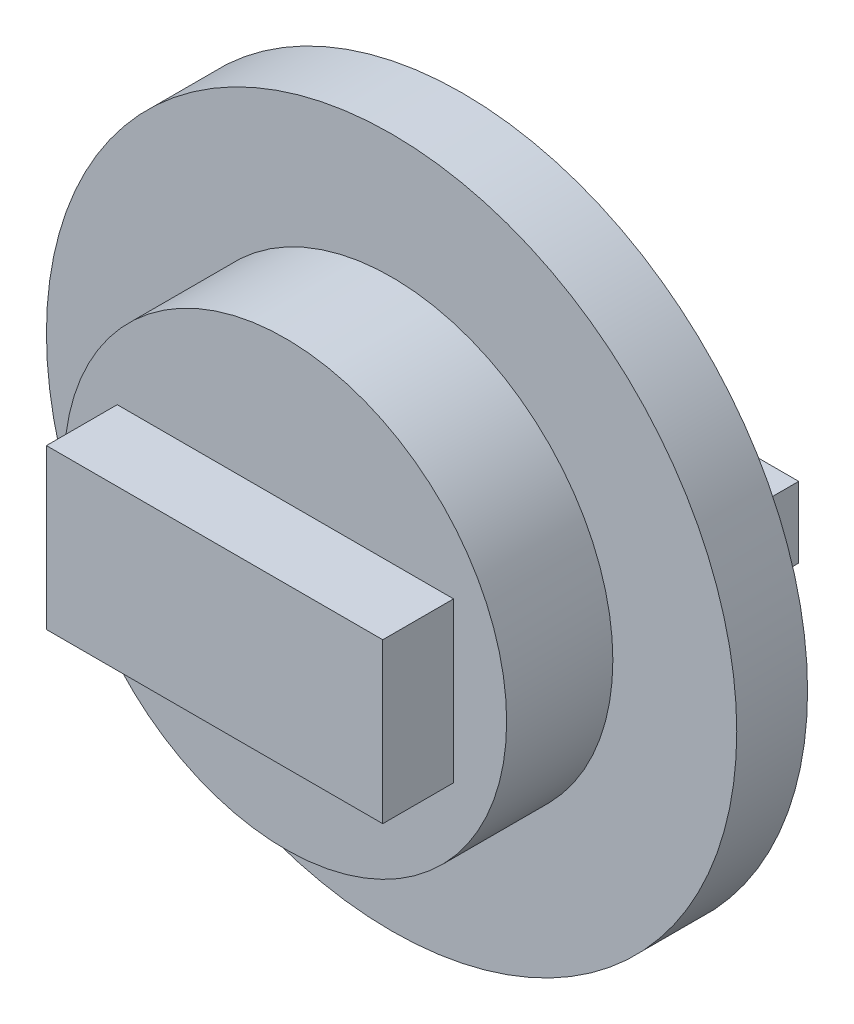
SolidWorks part; units mm, degrees
ref_plane "Спереди" through (0, 0, 0) normal (0, 0, 1) x (1, 0, 0)
ref_plane "Сверху" through (0, 0, 0) normal (0, 1, 0) x (1, 0, 0)
ref_plane "Справа" through (0, 0, 0) normal (1, 0, 0) x (0, 0, -1)
sketch "Эскиз1" plane through (0, 0, 0) normal (0, 0, 1) x (1, 0, 0)
  circle A0 centre (0, 0) radius 9.75
  dimension "D1" = 19.5
extrude "Бобышка-Вытянуть1" add sketch "Эскиз1" along normal blind 2
sketch "Эскиз2" plane through (0, 0, 0) normal (0, 0, 1) x (1, 0, 0)
  circle A0 centre (0, 0) radius 6.25
  dimension "D1" = 12.5
extrude "Бобышка-Вытянуть2" add sketch "Эскиз2" along normal blind 3 from offset 2
sketch "Эскиз3" plane through (0, 0, 0) normal (0, 0, 1) x (1, 0, 0)
  line L1 (-4.75, -2.25) -> (4.75, -2.25)
  line L2 (-4.75, -2.25) -> (-4.75, 2.25)
  line L3 (-4.75, 2.25) -> (4.75, 2.25)
  line L4 (4.75, -2.25) -> (4.75, 2.25)
  line L5 (-4.75, -2.25) -> (4.75, 2.25) construction
  line L6 (-4.75, 2.25) -> (4.75, -2.25) construction
  point P0 (0, 0)
  dimension "D1" = 4.5
  dimension "D2" = 9.5
extrude "Бобышка-Вытянуть3" add sketch "Эскиз3" along normal blind 2 from offset 5
sketch "Эскиз4" plane through (0, 0, 0) normal (0, 0, 1) x (1, 0, 0)
  line L0 (0, -1000) -> (0, 49000) construction
  line L1 (-7.5, 1) -> (7.5, 1)
  line L2 (-7.5, 1) -> (-7.5, 3)
  line L3 (-7.5, 3) -> (7.5, 3)
  line L4 (7.5, 1) -> (7.5, 3)
  line L5 (-7.5, 1) -> (7.5, 3) construction
  line L6 (-7.5, 3) -> (7.5, 1) construction
  line L7 (7.5, -3) -> (-7.5, -3)
  line L8 (7.5, -3) -> (7.5, -1)
  line L9 (7.5, -1) -> (-7.5, -1)
  line L10 (-7.5, -3) -> (-7.5, -1)
  line L11 (7.5, -3) -> (-7.5, -1) construction
  line L12 (7.5, -1) -> (-7.5, -3) construction
  point P0 (0, 2)
  point P5 (0, -2)
  point P10 (0, 0)
  point P11 (0, 0)
  dimension "D1" = 2
  dimension "D2" = 2
  dimension "D3" = 2
  dimension "D4" = 2
  dimension "D5" = 15
  dimension "D6" = 15
extrude "Бобышка-Вытянуть4" add sketch "Эскиз4" against normal blind 2
